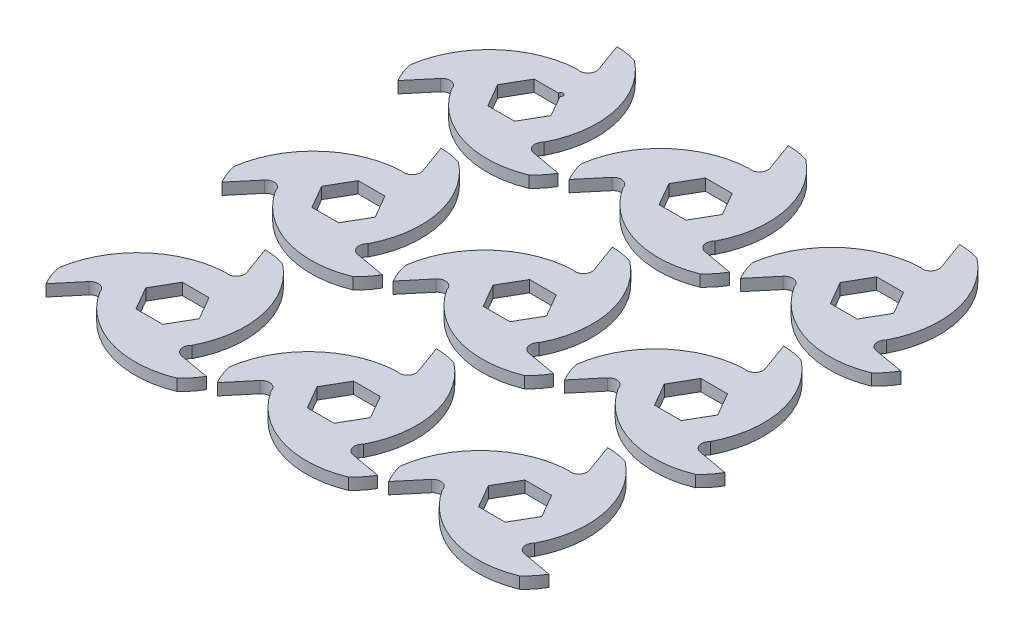
SolidWorks part; units mm, degrees
ref_plane "Front Plane" through (0, 0, 0) normal (0, 0, 1) x (1, 0, 0)
ref_plane "Top Plane" through (0, 0, 0) normal (0, 1, 0) x (1, 0, 0)
ref_plane "Right Plane" through (0, 0, 0) normal (1, 0, 0) x (0, 0, -1)
sketch "Sketch2" plane through (0, 0, 0) normal (0, 1, 0) x (1, 0, 0)
  line L0 (0, 50.8) -> (0, 0) construction
  line L1 (0, 0) -> (-43.9941, -25.4) construction
  line L2 (0, 0) -> (43.9941, -25.4) construction
  line L3 (0, 50.8) -> (5.6992, 35.1416)
  line L4 (43.9941, -25.4) -> (27.5839, -22.5064)
  line L5 (-43.9941, -25.4) -> (-33.2831, -12.6352)
  line L7 (7.3323, 12.7) -> (-7.3323, 12.7)
  line L8 (-7.3323, 12.7) -> (-14.6647, 0)
  line L9 (-14.6647, 0) -> (-7.3323, -12.7)
  line L10 (-7.3323, -12.7) -> (7.3323, -12.7)
  line L11 (7.3323, -12.7) -> (14.6647, 0)
  line L12 (14.6647, 0) -> (7.3323, 12.7)
  circle A0 centre (0, 0) radius 50.8 construction
  circle A1 centre (0, 13.2055) radius 37.5945
  circle A2 centre (11.4363, -6.6028) radius 37.5945
  circle A3 centre (-11.4363, -6.6028) radius 37.5945
  arc A4 (5.6992, 35.1416) -> (0, 29.21) centre (1.3938, 33.5746) cw
  arc A5 (27.5839, -22.5064) -> (25.2966, -14.605) centre (28.3796, -17.9943) cw
  arc A6 (-33.2831, -12.6352) -> (-25.2966, -14.605) centre (-29.7733, -15.5803) cw
  circle A7 centre (0, 0) radius 12.7 construction
  point P25 (0, 0)
  dimension "D1" = 101.6
  dimension "D4" = 20
  dimension "D6" = 30
  dimension "D2" = 120
  dimension "D3" = 120
  dimension "D5" = 21.59
  dimension "D8" = 25.4
  dimension "D7" = 3
extrude "Boss-Extrude2" add sketch "Sketch2" along normal mid plane 6.35 contours A1 A3 A2 L12 L11 L10 L9 L8 L7 | A1 A6 A2 A3 | L5 A6 A1 A3 | L4 A5 A3 A2 | A3 A5 A1 A2 | A2 A4 A3 A1 | L3 A4 A2 A1 region at (16.8055, 0, -37.817) region at (25.4344, 0, -14.5711) region at (-25.3361, 0, -14.7413) region at (-41.1532, 0, 4.3545) region at (18.3174, 0, -15.1298) region at (-0.0983, 0, 29.3123) region at (24.3477, 0, 33.4624)
sketch "Sketch3" plane through (0, 3.175, 0) normal (0, 1, 0) x (1, 0, 0)
  line L3 (43.9941, -25.4) -> (27.5839, -22.5064)
  line L4 (0, 50.8) -> (5.6992, 35.1416)
  line L5 (-43.9941, -25.4) -> (-33.2831, -12.6352)
  line L6 (43.9941, -25.4) -> (27.5839, -22.5064)
  line L7 (0, 50.8) -> (5.6992, 35.1416)
  line L8 (-43.9941, -25.4) -> (-33.2831, -12.6352)
  arc A0 (-48.1379, -14.7476) -> (0, 29.21) centre (2.2057, -21.5421) cw
  arc A1 (0, 29.21) -> (-43.9941, -25.4) centre (-11.4363, -6.6028) ccw construction
  arc A2 (0, 29.21) -> (5.6992, 35.1416) centre (1.3938, 33.5746) ccw construction
  arc A3 (11.2972, 49.0624) -> (25.2966, -14.605) centre (-19.7588, 8.8609) cw
  arc A4 (36.8407, -34.3148) -> (-25.2966, -14.605) centre (17.5532, 12.6812) cw
  arc A9 (-25.2966, -14.605) -> (-33.2831, -12.6352) centre (-29.7733, -15.5803) ccw
  arc A10 (-25.2966, -14.605) -> (43.9941, -25.4) centre (11.4363, -6.6028) ccw
  arc A11 (25.2966, -14.605) -> (27.5839, -22.5064) centre (28.3796, -17.9943) ccw
  arc A12 (25.2966, -14.605) -> (0, 50.8) centre (0, 13.2055) ccw
  arc A13 (0, 29.21) -> (5.6992, 35.1416) centre (1.3938, 33.5746) ccw
  arc A14 (0, 29.21) -> (-43.9941, -25.4) centre (-11.4363, -6.6028) ccw
  arc A15 (-25.2966, -14.605) -> (-33.2831, -12.6352) centre (-29.7733, -15.5803) ccw
  arc A16 (-25.2966, -14.605) -> (43.9941, -25.4) centre (11.4363, -6.6028) ccw
  arc A17 (25.2966, -14.605) -> (27.5839, -22.5064) centre (28.3796, -17.9943) ccw
  arc A18 (25.2966, -14.605) -> (0, 50.8) centre (0, 13.2055) ccw
  arc A19 (0, 29.21) -> (5.6992, 35.1416) centre (1.3938, 33.5746) ccw
  arc A20 (0, 29.21) -> (-43.9941, -25.4) centre (-11.4363, -6.6028) ccw
  point P26 (0, 0)
  arc M20 (-25.2966, -14.605) -> (43.9941, -25.4) centre (11.4363, -6.6028) ccw
  arc M23 (25.2966, -14.605) -> (0, 50.8) centre (0, 13.2055) ccw
  arc M26 (0, 29.21) -> (-43.9941, -25.4) centre (-11.4363, -6.6028) ccw
  dimension "D3" = 50.8
  dimension "D1" = 11.43
  dimension "D2" = 0
  dimension "D4" = 3
extrude "Cut-Extrude1" cut sketch "Sketch3" against normal through all contours A0 M26 | A3 M23 | A4 M20 region at (2.0677, 3.175, 36.1384) region at (30.2629, 3.175, -19.8599) region at (-32.3306, 3.175, -16.2785)
pattern_linear "LPattern1" count 3 spacing 96.52 along (0, 0, 1) count 3 spacing 93.98 along (1, 0, 0) of "Boss-Extrude2"
sketch "Sketch4" plane through (0, 3.175, 0) normal (0, 1, 0) x (1, 0, 0)
  circle A0 centre (7.3323, 12.7) radius 1.27
  dimension "D1" = 2.54
extrude "Cut-Extrude2" cut sketch "Sketch4" against normal through all
